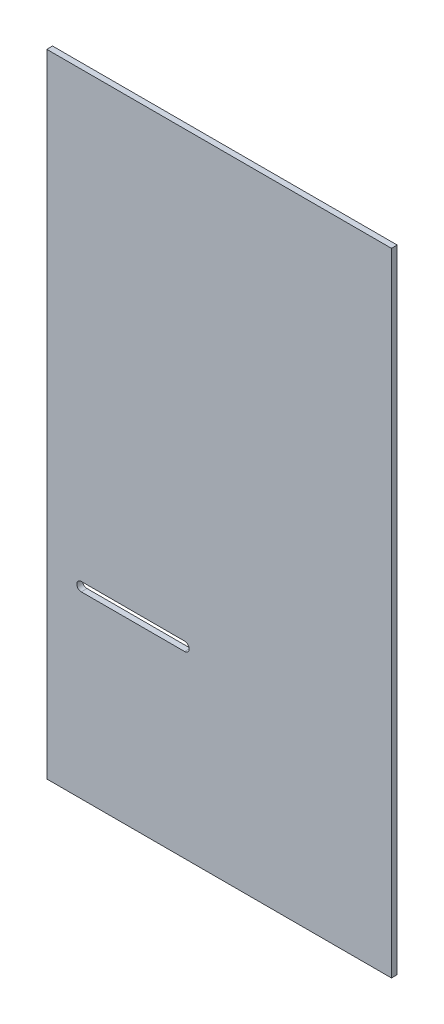
SolidWorks part; units mm, degrees
ref_plane "Front Plane" through (0, 0, 0) normal (1, 0, 0) x (0, 1, 0)
ref_plane "Top Plane" through (0, 0, 0) normal (0, 0, 1) x (0, 1, 0)
ref_plane "Right Plane" through (0, 0, 0) normal (0, 1, 0) x (-1, 0, 0)
sketch "Sketch1" plane through (0, 0, 0) normal (0, 0, 1) x (0, 1, 0)
  line L1 (-174.625, -95.25) -> (174.625, -95.25)
  line L2 (-174.625, -95.25) -> (-174.625, 95.25)
  line L3 (-174.625, 95.25) -> (174.625, 95.25)
  line L4 (174.625, -95.25) -> (174.625, 95.25)
  line L5 (-174.625, -95.25) -> (174.625, 95.25) construction
  line L6 (-174.625, 95.25) -> (174.625, -95.25) construction
  point P0 (0, 0)
  dimension "D1" = 349.25
  dimension "D2" = 190.5
extrude "Boss-Extrude1" add sketch "Sketch1" along normal blind 3.175
sketch "Sketch2" plane through (0, 0, 3.175) normal (0, 0, 1) x (1, 0, 0)
  line L0 (-95.25, 174.625) -> (-95.25, -174.625) construction
  line L1 (-95.25, -174.625) -> (95.25, -174.625) construction
  line L2 (-76.2, -75.5142) -> (-19.05, -75.5142)
  line L3 (-19.05, -70.5358) -> (-76.2, -70.5358)
  circle A0 centre (-76.2, -73.025) radius 2.4892 construction
  circle A1 centre (-19.05, -73.025) radius 2.4892 construction
  arc A2 (-76.2, -75.5142) -> (-76.2, -70.5358) centre (-76.2, -73.025) cw
  arc A3 (-19.05, -75.5142) -> (-19.05, -70.5358) centre (-19.05, -73.025) ccw
  point P0 (-19.05, -73.025)
  point P1 (-76.2, -73.025)
  dimension "D4" = 4.9784
  dimension "D1" = 57.15
  dimension "D2" = 19.05
  dimension "D3" = 101.6
extrude "Cut-Extrude1" cut sketch "Sketch2" against normal through all
